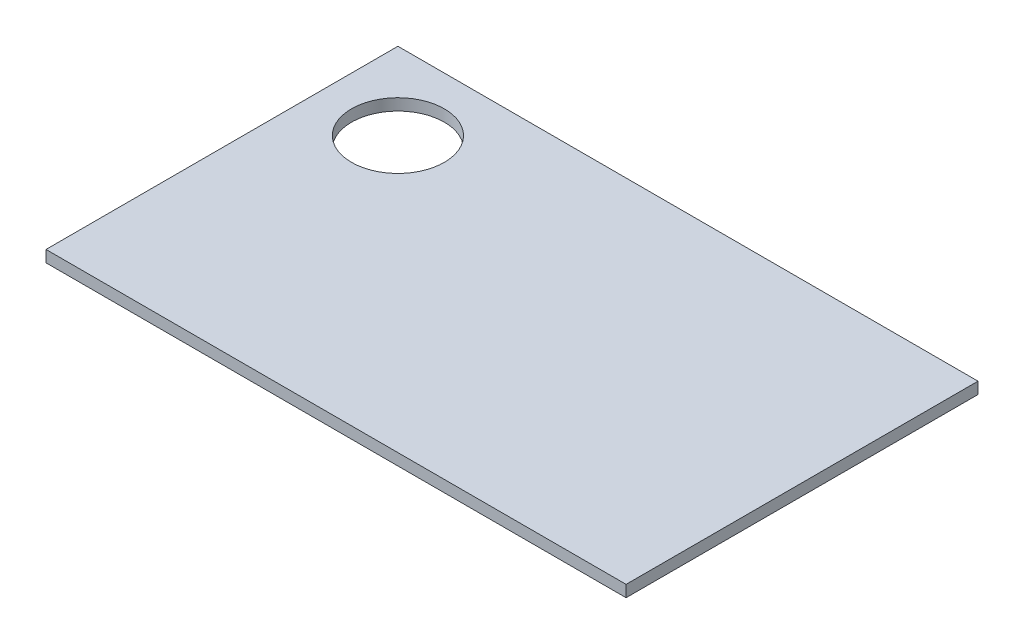
SolidWorks part; units mm, degrees
ref_plane "Front Plane" through (0, 0, 0) normal (0, 0, 1) x (1, 0, 0)
ref_plane "Top Plane" through (0, 0, 0) normal (0, 1, 0) x (1, 0, 0)
ref_plane "Right Plane" through (0, 0, 0) normal (1, 0, 0) x (0, 0, -1)
sketch "Sketch3" plane through (0, 711.2, 0) normal (0, 1, 0) x (1, 0, 0)
  line L0 (-476.25, 298.45) -> (-476.25, -285.75) construction
  line L2 (476.25, 298.45) -> (476.25, -285.75) construction
  line L3 (-476.25, 298.45) -> (476.25, 298.45) construction
  line L4 (-476.25, 298.45) -> (-476.25, -279.4)
  line L5 (-476.25, -279.4) -> (476.25, -279.4)
  line L6 (476.25, 298.45) -> (476.25, -279.4)
  line L7 (-476.25, 298.45) -> (476.25, 298.45)
  line L9 (-438.15, -279.4) -> (-476.25, -279.4) construction
  point P2 (476.25, -214.2541)
  point P8 (-476.25, -255.0024)
extrude "Boss-Extrude2" add sketch "Sketch3" against normal blind 19.05
sketch "Sketch4" plane through (0, 711.2, 0) normal (0, 1, 0) x (1, 0, 0)
  line L0 (476.25, 298.45) -> (-476.25, 298.45) construction
  line L1 (0, 95.25) -> (0, 0) construction
  line L2 (-203.2, 247.65) -> (203.2, 247.65) construction
  line L3 (-203.2, 247.65) -> (-203.2, 95.25) construction
  line L4 (-203.2, 95.25) -> (203.2, 95.25) construction
  line L5 (203.2, 247.65) -> (203.2, 95.25) construction
  line L6 (-349.25, 171.45) -> (-203.2, 171.45) construction
  line L7 (-476.25, 298.45) -> (-476.25, -279.4) construction
  circle A0 centre (-349.25, 171.45) radius 76.2
  point P11 (-306.5885, 171.45)
  dimension "D1" = 152.4
  dimension "D2" = 127
  dimension "D3" = 152.4
  dimension "D4" = 406.4
  dimension "D5" = 127
extrude "Cut-Extrude1" cut sketch "Sketch4" against normal through all
ref_plane "Filter Plane" through (0, 0, -171.45) normal (0, 0, 1) x (1, 0, 0)
